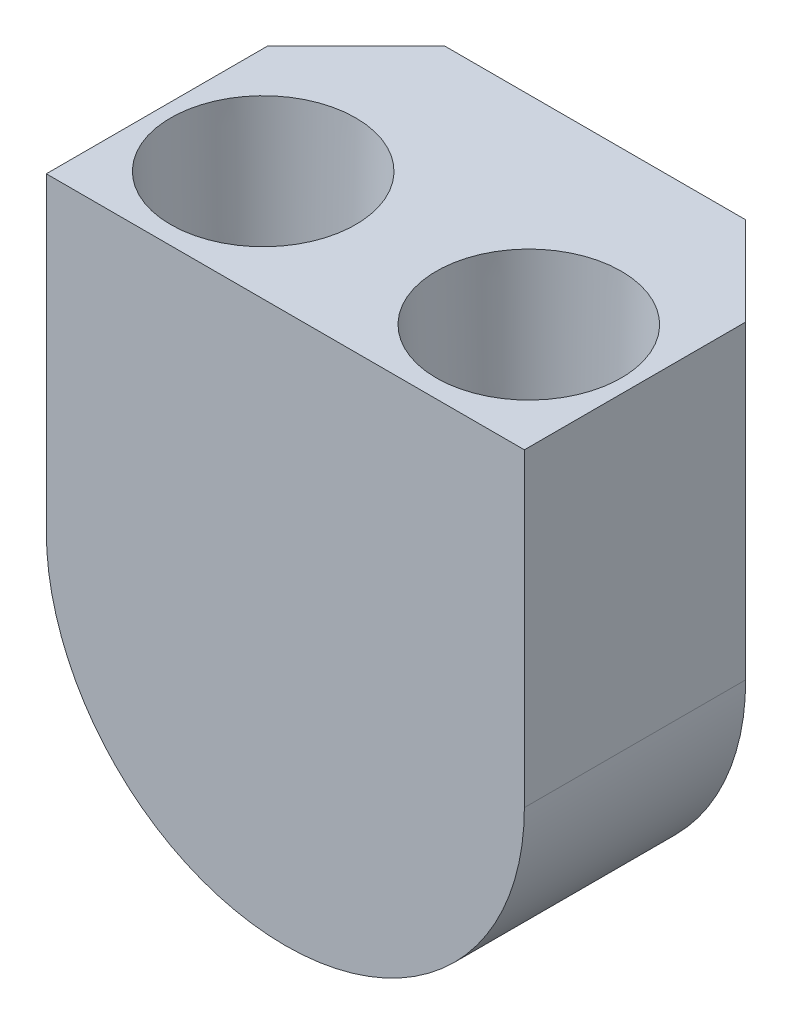
SolidWorks part; units mm, degrees
ref_plane "Front Plane" through (0, 0, 0) normal (0, 0, 1) x (1, 0, 0)
ref_plane "Top Plane" through (0, 0, 0) normal (0, 1, 0) x (1, 0, 0)
ref_plane "Right Plane" through (0, 0, 0) normal (1, 0, 0) x (0, 0, -1)
sketch "Sketch1" plane through (0, 0, 0) normal (0, 0, 1) x (1, 0, 0)
  line L2 (-8.4574, 9.1583) -> (-8.4574, 0.2683) construction
  line L3 (6.7826, 0.2683) -> (6.7826, 9.1583) construction
  line L4 (6.0206, 9.1583) -> (-7.6954, 9.1583)
  line L5 (-7.6954, 9.1583) -> (-7.6954, 0.2683)
  line L6 (6.0206, 0.2683) -> (6.0206, 9.1583)
  line L10 (6.7826, 0.2683) -> (6.7826, 9.1583) construction
  line L11 (-8.4574, 9.1583) -> (-8.4574, 0.2683) construction
  line L12 (-5.9174, 9.1583) -> (4.2426, 9.1583) construction
  arc A1 (-8.4574, 0.2683) -> (6.7826, 0.2683) centre (-0.8374, 0.2683) ccw construction
  arc A2 (-7.6954, 0.2683) -> (6.0206, 0.2683) centre (-0.8374, 0.2683) ccw
  arc A4 (-8.4574, 0.2683) -> (6.7826, 0.2683) centre (-0.8374, 0.2683) ccw construction
  dimension "D1" = 0.762
extrude "Boss-Extrude1" add sketch "Sketch1" against normal offset from surface (8.89 mm away) 3.81
chamfer "Chamfer1" distance 2.54 angle 45 3 edges at (-7.6954, 4.7133, -8.89) (-0.8374, -6.5897, -8.89) (6.0206, 4.7133, -8.89)
hole_wizard "Hole1" positions "Sketch2" profile "Sketch3" legacy
sketch "Sketch2" plane through (0, 9.1583, 0) normal (0, 1, 0) x (1, 0, 0)
  point P0 (2.9726, 3.175)
  point P2 (-4.6474, 3.175)
sketch "Sketch3" plane through (2.9726, 9.1583, -3.175) normal (1, 0, 0) x (0, 0, 1)
  line L0 (0, 0) -> (0, 3.81)
  line L1 (0, 3.81) -> (2.5273, 3.81)
  line L2 (2.5273, 3.81) -> (2.6543, 0)
  line L3 (2.6543, 0) -> (0, 0)
  line L4 (0, 110) -> (0, -10) construction
  dimension "Minor Diameter" = 5.0546
  dimension "Depth" = 3.81
  dimension "Major Diameter" = 5.3086
